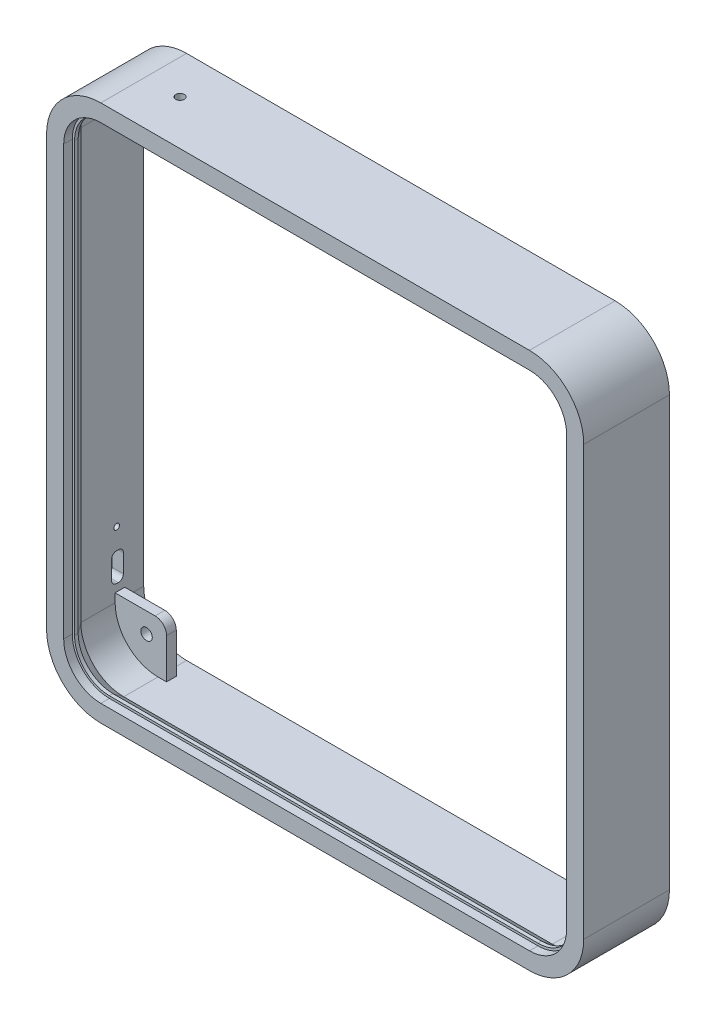
SolidWorks part; units mm, degrees
other "Markup1"
sketch "Sketch31" plane through (88, -88, 30) normal (0.191, -0.2603, 0.9464) x (0.9738, -0.0706, -0.2159)
ref_plane "Piano frontale" through (0, 0, 0) normal (0, 0, 1) x (1, 0, 0)
ref_plane "Piano superiore" through (0, 0, 0) normal (0, 1, 0) x (1, 0, 0)
ref_plane "Piano destro" through (0, 0, 0) normal (1, 0, 0) x (0, 0, -1)
sketch "Sketch2" plane through (0, 0, 0) normal (0, 0, 1) x (1, 0, 0)
  line L5 (-100, -88) -> (88, -88)
  line L6 (-100, -88) -> (-100, 100)
  line L7 (-100, 100) -> (88, 100)
  line L8 (88, -88) -> (88, 100)
  line L9 (-100, -88) -> (88, 100) construction
  line L10 (-100, 100) -> (88, -88) construction
  point P0 (-6, 6)
  dimension "D1" = 188
extrude "Boss-Extrude1" add sketch "Sketch2" along normal blind 30
fillet "Fillet1" radius 19 4 edges at (-100, -88, 15) (88, -88, 15) (88, 100, 15) (-100, 100, 15)
sketch "Sketch18" plane through (0, 0, 30) normal (0, 0, 1) x (1, 0, 0)
  line L0 (-93.2, 81) -> (-93.2, -69)
  line L1 (-81, -81.2) -> (69, -81.2)
  line L2 (81.2, -69) -> (81.2, 81)
  line L3 (69, 93.2) -> (-81, 93.2)
  line L4 (-100, 81) -> (-100, -69)
  line L5 (-81, -88) -> (69, -88)
  line L6 (88, -69) -> (88, 81)
  line L7 (69, 100) -> (-81, 100)
  line L8 (-100, 81) -> (-100, -69) construction
  line L9 (-81, -88) -> (69, -88) construction
  line L10 (88, -69) -> (88, 81) construction
  line L11 (69, 100) -> (-81, 100) construction
  arc A0 (-93.2, -69) -> (-81, -81.2) centre (-81, -69) ccw
  arc A1 (69, -81.2) -> (81.2, -69) centre (69, -69) ccw
  arc A2 (81.2, 81) -> (69, 93.2) centre (69, 81) ccw
  arc A3 (-81, 93.2) -> (-93.2, 81) centre (-81, 81) ccw
  arc A4 (-100, -69) -> (-81, -88) centre (-81, -69) ccw
  arc A5 (69, -88) -> (88, -69) centre (69, -69) ccw
  arc A6 (88, 81) -> (69, 100) centre (69, 81) ccw
  arc A7 (-81, 100) -> (-100, 81) centre (-81, 81) ccw
  arc A8 (-100, -69) -> (-81, -88) centre (-81, -69) ccw construction
  arc A9 (69, -88) -> (88, -69) centre (69, -69) ccw construction
  arc A10 (88, 81) -> (69, 100) centre (69, 81) ccw construction
  arc A11 (-81, 100) -> (-100, 81) centre (-81, 81) ccw construction
  dimension "D1" = 0
  dimension "D2" = 6.8
extrude "Cut-Extrude6" cut sketch "Sketch18" against normal blind 4
sketch "Sketch19" plane through (0, 0, 0) normal (0, 0, -1) x (-1, 0, 0)
  line L8 (-69, -84) -> (81, -84)
  line L9 (96, -69) -> (96, 81)
  line L10 (81, 96) -> (-69, 96)
  line L11 (-84, 81) -> (-84, -69)
  line L12 (-69, -84) -> (81, -84)
  line L13 (96, -69) -> (96, 81)
  line L14 (81, 96) -> (-69, 96)
  line L15 (-84, 81) -> (-84, -69)
  arc A8 (81, -84) -> (96, -69) centre (81, -69) ccw
  arc A9 (96, 81) -> (81, 96) centre (81, 81) ccw
  arc A10 (-69, 96) -> (-84, 81) centre (-69, 81) ccw
  arc A11 (-84, -69) -> (-69, -84) centre (-69, -69) ccw
  arc A12 (81, -84) -> (96, -69) centre (81, -69) ccw
  arc A13 (96, 81) -> (81, 96) centre (81, 81) ccw
  arc A14 (-69, 96) -> (-84, 81) centre (-69, 81) ccw
  arc A15 (-84, -69) -> (-69, -84) centre (-69, -69) ccw
  dimension "D1" = 4
extrude "Cut-Extrude8-svuotamento" cut sketch "Sketch19" against normal up to surface (26 mm away) up to face at (-6, 6, 26)
sketch "Sketch20" plane through (0, 0, 30) normal (0, 0, 1) x (1, 0, 0)
  line L8 (-94, 81) -> (-94, -69)
  line L9 (-81, -82) -> (69, -82)
  line L10 (82, -69) -> (82, 81)
  line L11 (69, 94) -> (-81, 94)
  line L12 (-94, 81) -> (-94, -69)
  line L13 (-81, -82) -> (69, -82)
  line L14 (82, -69) -> (82, 81)
  line L15 (69, 94) -> (-81, 94)
  arc A8 (-94, -69) -> (-81, -82) centre (-81, -69) ccw
  arc A9 (69, -82) -> (82, -69) centre (69, -69) ccw
  arc A10 (82, 81) -> (69, 94) centre (69, 81) ccw
  arc A11 (-81, 94) -> (-94, 81) centre (-81, 81) ccw
  arc A12 (-94, -69) -> (-81, -82) centre (-81, -69) ccw
  arc A13 (69, -82) -> (82, -69) centre (69, -69) ccw
  arc A14 (82, 81) -> (69, 94) centre (69, 81) ccw
  arc A15 (-81, 94) -> (-94, 81) centre (-81, 81) ccw
  dimension "D1" = 6
extrude "Cut-Extrude9-alloggiamento-finestra" cut sketch "Sketch20" against normal blind 3
sketch "Sketch22" plane through (0, 0, 0) normal (0, 0, -1) x (-1, 0, 0)
  line L0 (-66, 78) -> (-86, 78)
  line L1 (-86, -66) -> (-66, -66)
  line L4 (-66, -66) -> (-66, -86)
  line L5 (-86, -66) -> (-66, -86) construction
  line L6 (-81.0208, -81.0208) -> (-66, -66) construction
  line L7 (-66, 98) -> (-66, 78)
  line L8 (-69, -86) -> (81, -86)
  line L9 (98, -69) -> (98, 81)
  line L10 (81, 98) -> (-69, 98)
  line L11 (-86, 81) -> (-86, -69)
  line L12 (-69, -86) -> (81, -86) construction
  line L13 (98, -69) -> (98, 81) construction
  line L14 (81, 98) -> (-69, 98) construction
  line L15 (-86, 81) -> (-86, -69) construction
  line L16 (78, 78) -> (78, 98)
  line L17 (98, 78) -> (78, 78)
  line L18 (78, -66) -> (98, -66)
  line L19 (78, -86) -> (78, -66)
  arc A8 (81, -86) -> (98, -69) centre (81, -69) ccw
  arc A9 (98, 81) -> (81, 98) centre (81, 81) ccw
  arc A10 (-69, 98) -> (-86, 81) centre (-69, 81) ccw
  arc A11 (-86, -69) -> (-69, -86) centre (-69, -69) ccw
  arc A12 (81, -86) -> (98, -69) centre (81, -69) ccw construction
  arc A13 (98, 81) -> (81, 98) centre (81, 81) ccw construction
  arc A14 (-69, 98) -> (-86, 81) centre (-69, 81) ccw construction
  arc A15 (-86, -69) -> (-69, -86) centre (-69, -69) ccw construction
  point P4 (-76, -76)
  point P6 (-69, -69)
  line M14 (81, -84) -> (-69, -84)
  arc M15 (-69, -84) -> (-84, -69) centre (-69, -69) cw
  line M16 (-84, -69) -> (-84, 81)
  arc M17 (-84, 81) -> (-69, 96) centre (-69, 81) cw
  line M18 (-69, 96) -> (81, 96)
  arc M19 (81, 96) -> (96, 81) centre (81, 81) cw
  line M20 (96, 81) -> (96, -69)
  arc M21 (96, -69) -> (81, -84) centre (81, -69) cw
  dimension "D2" = 4
  dimension "D3" = 20
  dimension "D1" = 2
extrude "Boss-Extrude2" add sketch "Sketch22" against normal blind 10 contours L7 L0 M18 M17 M16 | L17 L16 M20 M19 M18 | L19 L18 M14 M21 M20 | L4 L1 M16 M15 M14 region at (74.0106, 86.0106, 0) region at (74.0106, -74.0106, 0) region at (-86.0106, 86.0106, 0) region at (-86.0106, -74.0106, 0)
fillet "Fillet4" radius 4 4 edges at (-78, -66, 5) (66, -66, 5) (66, 78, 5) (-78, 78, 5)
hole_wizard "Ø4.0mm Dowel Hole2" positions "Sketch28" profile "Sketch29" hole size "Ø4.0" standard "ANSI Metric" end condition through all
sketch "Sketch28" plane through (0, 0, 0) normal (0, 0, -1) x (-1, 0, 0)
  line L0 (-73, 85) -> (-66, 85) construction
  line L1 (-66, 96) -> (-66, 82) construction
  line L4 (-73, 85) -> (-73, 78) construction
  line L5 (-70, 78) -> (-84, 78) construction
  line L6 (85, -66) -> (85, -73) construction
  line L7 (82, -66) -> (96, -66) construction
  line L8 (85, -73) -> (78, -73)
  line L9 (78, -84) -> (78, -70) construction
  point P0 (-73, 85)
  point P9 (85, 85)
  point P10 (85, -73)
  point P11 (-73, -73)
  dimension "D2" = 7
  dimension "D1" = 4
sketch "Sketch29" plane through (73, 85, 0) normal (1, 0, 0) x (0, 1, 0)
  line L0 (0, 0) -> (0, 30)
  line L1 (0, 30) -> (2, 30)
  line L2 (2, 30) -> (2, 0)
  line L5 (2, 0) -> (0, 0)
  line L11 (0, -6.35) -> (0, 107.95) construction
  dimension "Thru Hole Dia." = 4
  dimension "Thru Hole Depth" = 30
sketch "Sketch30" plane through (0, 0, 0) normal (0, 0, -1) x (-1, 0, 0)
  line L8 (-69, -84) -> (81, -84)
  line L9 (96, -69) -> (96, 81)
  line L10 (81, 96) -> (-69, 96)
  line L11 (-84, 81) -> (-84, -69)
  line L12 (-69, -84) -> (81, -84)
  line L13 (96, -69) -> (96, 81)
  line L14 (81, 96) -> (-69, 96)
  line L15 (-84, 81) -> (-84, -69)
  arc A8 (81, -84) -> (96, -69) centre (81, -69) ccw
  arc A9 (96, 81) -> (81, 96) centre (81, 81) ccw
  arc A10 (-69, 96) -> (-84, 81) centre (-69, 81) ccw
  arc A11 (-84, -69) -> (-69, -84) centre (-69, -69) ccw
  arc A12 (81, -84) -> (96, -69) centre (81, -69) ccw
  arc A13 (96, 81) -> (81, 96) centre (81, 81) ccw
  arc A14 (-69, 96) -> (-84, 81) centre (-69, 81) ccw
  arc A15 (-84, -69) -> (-69, -84) centre (-69, -69) ccw
  dimension "D1" = 4
extrude "Cut-Extrude10" cut sketch "Sketch30" against normal blind 6.6
sketch "Sketch11" plane through (0, 100, 0) normal (0, 1, 0) x (1, 0, 0)
  circle A0 centre (-68.955, -14.3249) radius 1.5
extrude "Cut-Extrude4" cut sketch "Sketch11" against normal up to next
sketch "Sketch15" plane through (-100, 0, 0) normal (1, 0, 0) x (0, 0, -1)
  line L8 (-8.9002, -53.4953) -> (-9.4602, -53.4953)
  line L9 (-7.1002, -55.2953) -> (-7.1002, -61.6453)
  line L10 (-8.9002, -63.4453) -> (-9.4602, -63.4453)
  line L11 (-11.2602, -55.2953) -> (-11.2602, -61.6453)
  line L12 (-7.1002, -53.4953) -> (-11.2602, -63.4453) construction
  line L13 (-7.1002, -63.4453) -> (-11.2602, -53.4953) construction
  circle A9 centre (-9.4602, -46.2279) radius 1
  arc A10 (-7.1002, -61.6453) -> (-8.9002, -63.4453) centre (-8.9002, -61.6453) cw
  arc A11 (-9.4602, -63.4453) -> (-11.2602, -61.6453) centre (-9.4602, -61.6453) cw
  arc A12 (-9.4602, -53.4953) -> (-11.2602, -55.2953) centre (-9.4602, -55.2953) ccw
  arc A13 (-8.9002, -53.4953) -> (-7.1002, -55.2953) centre (-8.9002, -55.2953) cw
  point P12 (-9.1802, -58.4703)
  dimension "D3" = 2
  dimension "D4" = 1.8
  dimension "D1" = 9.95
  dimension "D2" = 4.16
extrude "Cut-Extrude5" cut sketch "Sketch15" along normal up to next
chamfer "Chamfer1" distance 4 distance2 3 8 edges at (-6, -84, 26) (-91.6066, -79.6066, 26) (79.6066, -79.6066, 26) (-96, 6, 26) (84, 6, 26) (-91.6066, 91.6066, 26) (79.6066, 91.6066, 26) (-6, 96, 26) first distance on face at (-6, -84, 9.8667) first distance on face at (-90.0533, -78.0533, 18) first distance on face at (78.0533, -78.0533, 18) first distance on face at (-96, -58.4703, 9.1802) first distance on face at (84, 6, 9.8667) first distance on face at (-90.0533, 90.0533, 18) first distance on face at (78.0533, 90.0533, 18) first distance on face at (-68.955, 96, 15.8249)
